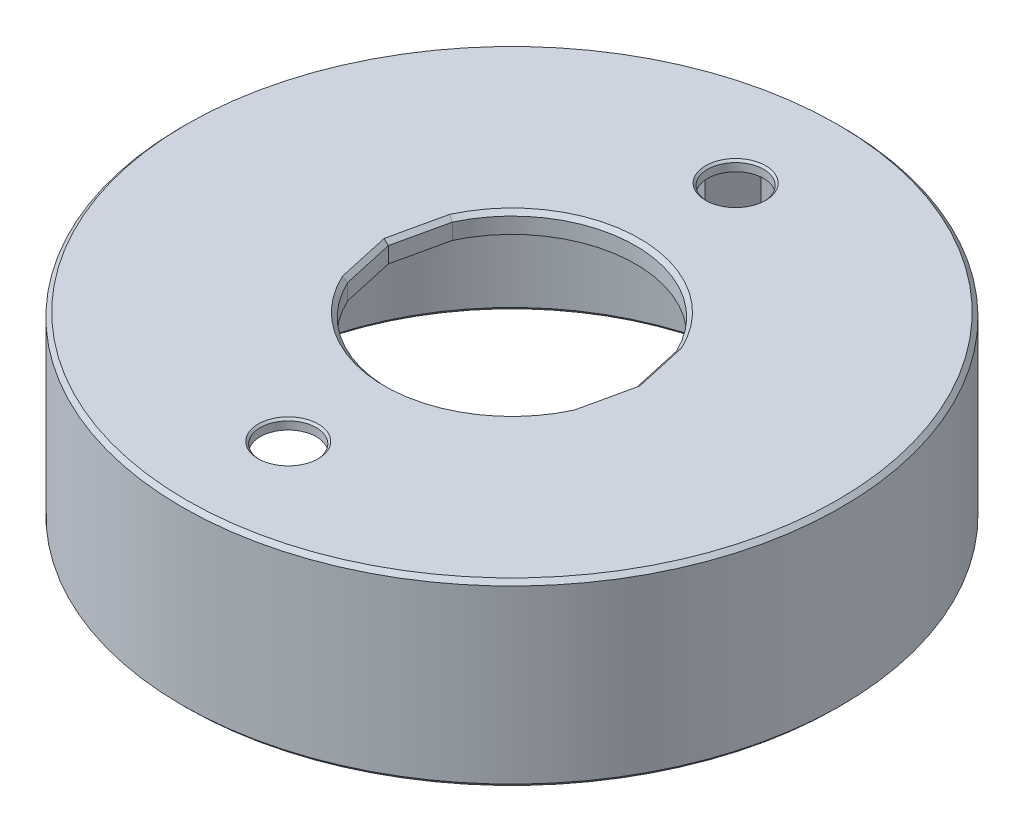
SolidWorks part; units mm, degrees
ref_plane "Front Plane" through (0, 0, 0) normal (0, 0, 1) x (1, 0, 0)
ref_plane "Top Plane" through (0, 0, 0) normal (0, 1, 0) x (1, 0, 0)
ref_plane "Right Plane" through (0, 0, 0) normal (1, 0, 0) x (0, 0, -1)
sketch "Sketch1" plane through (0, 0, 0) normal (0, 1, 0) x (1, 0, 0)
  circle A0 centre (0, 0) radius 12.73
  circle A1 centre (0, 0) radius 16.5
  dimension "D1" = 3.77
  dimension "D2" = 33
extrude "Boss-Extrude1" add sketch "Sketch1" along normal blind 8
sketch "Sketch2" plane through (0, 8, 0) normal (0, 1, 0) x (1, 0, 0)
  circle A0 centre (0, 0) radius 16.5
extrude "Boss-Extrude2" add sketch "Sketch2" along normal blind 1
sketch "Sketch3" plane through (0, 9, 0) normal (0, 1, 0) x (1, 0, 0)
  line L0 (0, 13) -> (0, 11.2)
  line L1 (0, -13) -> (0, -11.2)
  line L2 (0, -13) -> (3.3, -13)
  line L3 (0, -13) -> (-3.3, -13)
  line L4 (0, 13) -> (-3.3, 13)
  line L5 (0, 13) -> (3.3, 13)
  line L6 (-6.1875, 0) -> (-3.3, -13)
  line L7 (6.1875, 0) -> (3.3, -13)
  line L8 (-3.3, 13) -> (-6.1875, 0)
  line L9 (3.3, 13) -> (6.1875, 0)
  circle A0 centre (0, 0) radius 6.1875
  circle A4 centre (0, 11.2) radius 1.4025
  circle A5 centre (0, -11.2) radius 1.4025
  dimension "D1" = 12.375
  dimension "D7" = 1.8
  dimension "D8" = 2.805
  dimension "D9" = 1.8
  dimension "D10" = 2.805
  dimension "D2" = 13
  dimension "D3" = 13
  dimension "D4" = 3.3
  dimension "D5" = 3.3
  dimension "D6" = 3.3
  dimension "D11" = 3.3
extrude "Cut-Extrude1" cut sketch "Sketch3" against normal blind 12 contours L9 A0 L8 L6 L7 | A4 | A5 region at (0.9637, 9, -12.1637) region at (0, 9, 0) region at (-0.9637, 9, 10.2363)
sketch "Sketch4" plane through (0, 8, 0) normal (0, -1, 0) x (1, 0, 0)
  line L1 (3.4641, 11.2) -> (1.7321, 14.2)
  line L2 (1.7321, 14.2) -> (-1.7321, 14.2)
  line L3 (-1.7321, 14.2) -> (-3.4641, 11.2)
  line L4 (-3.4641, 11.2) -> (-1.7321, 8.2)
  line L5 (-1.7321, 8.2) -> (1.7321, 8.2)
  line L6 (1.7321, 8.2) -> (3.4641, 11.2)
  circle A0 centre (0, 11.2) radius 3 construction
  dimension "D1" = 6
extrude "Cut-Extrude2" cut sketch "Sketch4" along normal blind 12
sketch "Sketch5" plane through (0, 8, 0) normal (0, -1, 0) x (1, 0, 0)
  line L1 (3.4416, 11.2) -> (1.7208, 14.1806)
  line L2 (1.7208, 14.1806) -> (-1.7208, 14.1806)
  line L3 (-1.7208, 14.1806) -> (-3.4416, 11.2)
  line L4 (-3.4416, 11.2) -> (-1.7208, 8.2194)
  line L5 (-1.7208, 8.2194) -> (1.7208, 8.2194)
  line L6 (1.7208, 8.2194) -> (3.4416, 11.2)
  circle A0 centre (0, 11.2) radius 2.9806 construction
extrude "Cut-Extrude3" cut sketch "Sketch5" against normal blind 0.5
sketch "Sketch6" plane through (0, 8, 0) normal (0, -1, 0) x (1, 0, 0)
  line L1 (3.4641, -11.2) -> (1.7321, -8.2)
  line L2 (1.7321, -8.2) -> (-1.7321, -8.2)
  line L3 (-1.7321, -8.2) -> (-3.4641, -11.2)
  line L4 (-3.4641, -11.2) -> (-1.7321, -14.2)
  line L5 (-1.7321, -14.2) -> (1.7321, -14.2)
  line L6 (1.7321, -14.2) -> (3.4641, -11.2)
  circle A0 centre (0, -11.2) radius 3 construction
  dimension "D1" = 6
extrude "Cut-Extrude4" cut sketch "Sketch6" along normal blind 17.5
sketch "Sketch7" plane through (0, 8, 0) normal (0, -1, 0) x (1, 0, 0)
  line L1 (3.4876, -11.2) -> (1.7438, -8.1797)
  line L2 (1.7438, -8.1797) -> (-1.7438, -8.1797)
  line L3 (-1.7438, -8.1797) -> (-3.4876, -11.2)
  line L4 (-3.4876, -11.2) -> (-1.7438, -14.2203)
  line L5 (-1.7438, -14.2203) -> (1.7438, -14.2203)
  line L6 (1.7438, -14.2203) -> (3.4876, -11.2)
  circle A0 centre (0, -11.2) radius 3.0203 construction
extrude "Cut-Extrude5" cut sketch "Sketch7" against normal blind 0.5
scale "Scale1" scale about centroid uniform scaling yes scale factor 1.212121
chamfer "Chamfer1" distance 0.25 angle 45 7 edges at (-7.1474, 9.8616, 1.5873) (-7.1474, 9.8616, -1.5878) (0, 9.8616, -7.5003) (7.1474, 9.8616, -1.5878) (7.1474, 9.8616, 1.5873) (0, 9.8616, 7.4997) (0, 9.8616, 19.9997)
chamfer "Chamfer2" distance 0.125 angle 45 2 edges at (0, 9.8616, -11.8761) (0, 9.8616, 15.2755)
chamfer "Chamfer3" distance 0.25 angle 45 8 edges at (2.7194, -1.0474, -16.1387) (0, -1.0474, -17.2124) (-2.7194, -1.0474, -16.1387) (-15.4303, -1.0474, -0.0003) (-2.7194, -1.0474, 16.1381) (0, -1.0474, 17.2118) (2.7194, -1.0474, 16.1381) (15.4303, -1.0474, -0.0003)
chamfer "Chamfer4" distance 0.25 angle 45 1 edges at (0, -1.0474, 19.9997)
